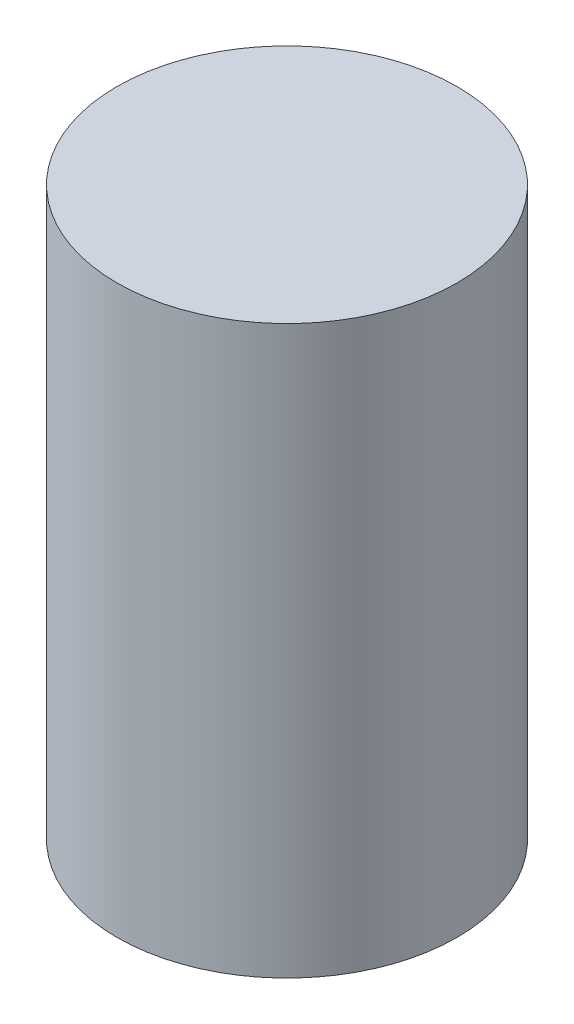
SolidWorks part; units mm, degrees
ref_plane "Front Plane" through (0, 0, 0) normal (0, 0, 1) x (1, 0, 0)
ref_plane "Top Plane" through (0, 0, 0) normal (0, 1, 0) x (1, 0, 0)
ref_plane "Right Plane" through (0, 0, 0) normal (1, 0, 0) x (0, 0, -1)
sketch "Sketch1" plane through (0, 0, 0) normal (0, 1, 0) x (1, 0, 0)
  circle A0 centre (0, 0) radius 38.1
  dimension "D1" = 76.2
extrude "Boss-Extrude1" add sketch "Sketch1" along normal blind 127
ref_axis "Axis1" through (0, 133.35, 0) along (0, -1, 0)
